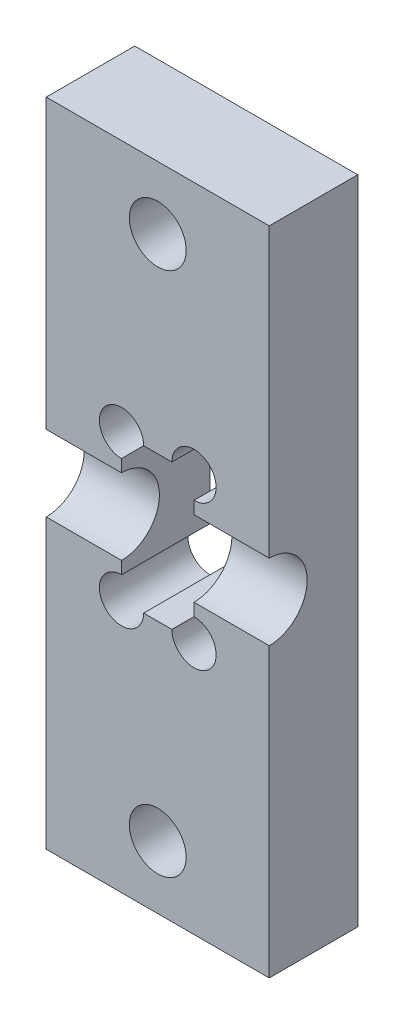
SolidWorks part; units mm, degrees
ref_plane "Top Plane" through (0, 0, 0) normal (0, 0, 1) x (1, 0, 0)
ref_plane "Front Plane" through (0, 0, 0) normal (0, 1, 0) x (1, 0, 0)
ref_plane "Right Plane" through (0, 0, 0) normal (1, 0, 0) x (0, 0, -1)
sketch "Sketch1" plane through (0, 0, 0) normal (0, 0, 1) x (1, 0, 0)
  line L0 (13.25, 24.6944) -> (13.25, 33.7256)
  line L1 (0, 0) -> (20, 0)
  line L2 (0, 0) -> (0, 58.42)
  line L3 (0, 58.42) -> (20, 58.42)
  line L4 (20, 0) -> (20, 58.42)
  line L5 (11.2656, 35.71) -> (8.7344, 35.71)
  line L6 (6.75, 33.7256) -> (6.75, 24.6944)
  line L7 (8.7344, 22.71) -> (11.2656, 22.71)
  line L8 (10, 52.78) -> (10, 5.64) construction
  circle A0 centre (10, 52.78) radius 2.55
  circle A1 centre (10, 5.64) radius 2.55
  arc A4 (13.25, 24.6944) -> (11.2656, 22.71) centre (13.25, 22.71) cw
  arc A5 (8.7344, 22.71) -> (6.75, 24.6944) centre (6.75, 22.71) cw
  arc A6 (6.75, 33.7256) -> (8.7344, 35.71) centre (6.75, 35.71) cw
  arc A7 (13.25, 33.7256) -> (11.2656, 35.71) centre (13.25, 35.71) ccw
  point P22 (13.25, 29.21)
  point P23 (20, 29.21)
  point P24 (10, 35.71)
  point P25 (10, 58.42)
  point P26 (10, 29.21)
  dimension "D1" = 13
  dimension "D3" = 1.9844
  dimension "D4" = 5.1
  dimension "D2" = 6.5
  dimension "D5" = 58.42
  dimension "D6" = 47.14
  dimension "D7" = 20
extrude "Boss-Extrude1" add sketch "Sketch1" along normal blind 7.9375
sketch "Sketch2" plane through (20, 0, 0) normal (1, 0, 0) x (0, 0, -1)
  line L0 (-7.9375, 0) -> (-7.9375, 58.42) construction
  line L1 (-7.9375, 32.61) -> (-7.9375, 25.81)
  arc A0 (-7.9375, 25.81) -> (-7.9375, 32.61) centre (-7.9375, 29.21) ccw
  dimension "D1" = 3.4
extrude "Cut-Extrude1" cut sketch "Sketch2" against normal through all
cosmetic thread "Cosmetic Thread1" parameters "D2"=10
cosmetic thread "Cosmetic Thread2" parameters "D2"=10
